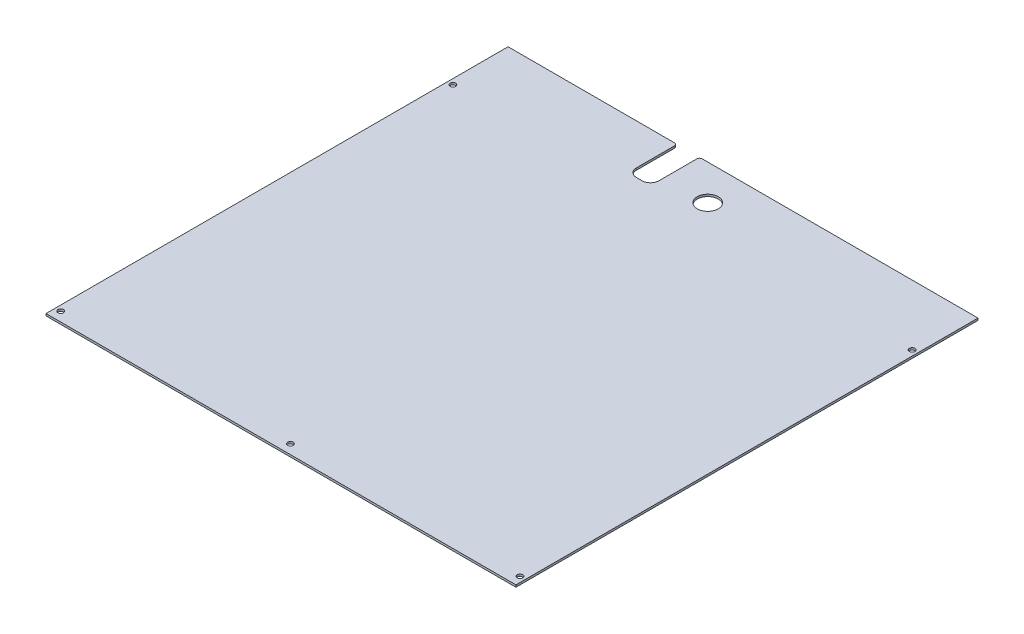
SolidWorks part; units mm, degrees
note: The reader was unsure of these and kept them because the rebuilt part matched: thickness of "Brida base2", "Chapa metálica(12)", "Chapa metálica(21)", "Chapa metálica(22)", "Chapa metálica(23)".
material "Poliestireno"
ref_plane "Alzado" through (0, 0, 0) normal (0, 0, 1) x (1, 0, 0)
ref_plane "Planta" through (0, 0, 0) normal (0, 1, 0) x (1, 0, 0)
ref_plane "Vista lateral" through (0, 0, 0) normal (1, 0, 0) x (0, 0, -1)
sketch "Croquis12" plane through (0, 0, 0) normal (0, 1, 0) x (1, 0, 0)
  line L0 (0, 0) -> (0, 121.41) construction
  line L1 (-167.5, -207.99) -> (167.5, -207.99)
  line L2 (-167.5, -207.99) -> (-167.5, 121.41)
  line L3 (-167.5, 121.41) -> (167.5, 121.41)
  line L4 (167.5, -207.99) -> (167.5, 121.41)
  point P14 (167.5, 121.41)
  point P17 (-167.5, 121.41)
  dimension "D1" = 335
  dimension "D2" = 207.99
  dimension "D3" = 121.41
base flange "Brida base2" sketch "Croquis12" thickness 1.5 reverse thickness direction no parameters "D1"=1
sketch "Croquis25" plane through (0, 0, 0) normal (0, 1, 0) x (1, 0, 0)
  line L0 (0, 0) -> (0, -48.7685) construction
  line L2 (-159.058, -201.3) -> (150.1867, -201.3) construction
  dimension "D2" = 201.3
sketch "Croquis27" plane through (0, 0, 0) normal (0, 1, 0) x (1, 0, 0)
  line L0 (0, 0) -> (0, -88.775) construction
  line L1 (-159.058, -201.3) -> (150.1867, -201.3) construction
  line L2 (-163.7, -201.3) -> (163.7, -201.3) construction
  circle A0 centre (-163.7, -201.3) radius 2
  circle A1 centre (-163.7, 78.26) radius 2
  circle A2 centre (163.7, 78.26) radius 2
  circle A3 centre (163.7, -201.3) radius 2
  circle A4 centre (0, -201.3) radius 2
  dimension "D1" = 4
  dimension "D4" = 327.4
  dimension "D2" = 78.26
extrude "Cortar-Extruir6" cut sketch "Croquis27" against normal up to next normal cut yes
sketch "Croquis28" plane through (0, 0, 0) normal (0, 1, 0) x (1, 0, 0)
  line L1 (-167.5, -207.99) -> (167.5, -207.99) construction
  circle A0 centre (0, 96.25) radius 7.5
  dimension "D1" = 304.24
  dimension "D2" = 15
extrude "Cortar-Extruir7" cut sketch "Croquis28" against normal up to next normal cut yes
sketch "Croquis29" plane through (0, 0, 0) normal (0, 1, 0) x (1, 0, 0)
  line L0 (-39, 86.41) -> (-39, 125.7663) construction
  line L1 (-47, 121.41) -> (-31, 121.41)
  line L2 (-47, 121.41) -> (-47, 86.41)
  line L3 (-47, 86.41) -> (-31, 86.41)
  line L4 (-31, 121.41) -> (-31, 86.41)
  line L5 (167.5, 121.41) -> (-167.5, 121.41) construction
  circle A2 centre (0, 96.25) radius 7.5 construction
  dimension "D1" = 39
  dimension "D2" = 16
  dimension "D3" = 35
extrude "Cortar-Extruir8" cut sketch "Croquis29" against normal through all normal cut yes
fillet "Redondeo1" radius 6 2 edges at (-31, -0.75, -86.41) (-47, -0.75, -86.41)
fillet "Redondeo2" radius 2 2 edges at (-31, -0.75, -121.41) (-47, -0.75, -121.41)
sketch "Líneas de pliegue3" [suppressed] plane through (0, 0, 0) normal (0, 1, 0) x (1, 0, 0)
sketch "Cuadro delimitador3" [suppressed] plane through (0, 0, 0) normal (0, 1, 0) x (1, 0, 0)
sheet metal parameters "Chapa metálica(12)" thickness 1.5 parameters "D1"=1
flat pattern "Chapa desplegada(12)" [suppressed]
sketch "Líneas de pliegue4" plane through (0, 0, 0) normal (0, 1, 0) x (1, 0, 0)
sketch "Cuadro delimitador4" [suppressed] plane through (0, 0, 0) normal (0, 1, 0) x (1, 0, 0)
sheet metal parameters "Chapa metálica(21)" thickness 1.5 parameters "D1"=1, "D7"=3
flat pattern "Chapa desplegada(12)"
sketch "Líneas de pliegue4" plane through (0, 0, 0) normal (0, 1, 0) x (1, 0, 0)
sketch "Cuadro delimitador4" [suppressed] plane through (0, 0, 0) normal (0, 1, 0) x (1, 0, 0)
sheet metal parameters "Chapa metálica(22)" thickness 1.5 parameters "D1"=1, "D7"=3
flat pattern "Chapa desplegada(12)"
sketch "Líneas de pliegue4" plane through (0, 0, 0) normal (0, 1, 0) x (1, 0, 0)
sketch "Cuadro delimitador4" [suppressed] plane through (0, 0, 0) normal (0, 1, 0) x (1, 0, 0)
sheet metal parameters "Chapa metálica(23)" thickness 1.5 parameters "D1"=1, "D7"=3
flat pattern "Chapa desplegada(12)"
sketch "Líneas de pliegue4" plane through (0, 0, 0) normal (0, 1, 0) x (1, 0, 0)
sketch3d "Cuadro delimitador4" [suppressed]
  line L0 (167.5, 121.41, 0) -> (-167.5, 121.41, 0) construction
  line L1 (167.5, -207.99, 0) -> (-167.5, -207.99, 0) construction
  line L2 (167.5, 121.41, 0) -> (167.5, -207.99, 0) construction
  line L3 (-167.5, 121.41, 0) -> (-167.5, -207.99, 0) construction
